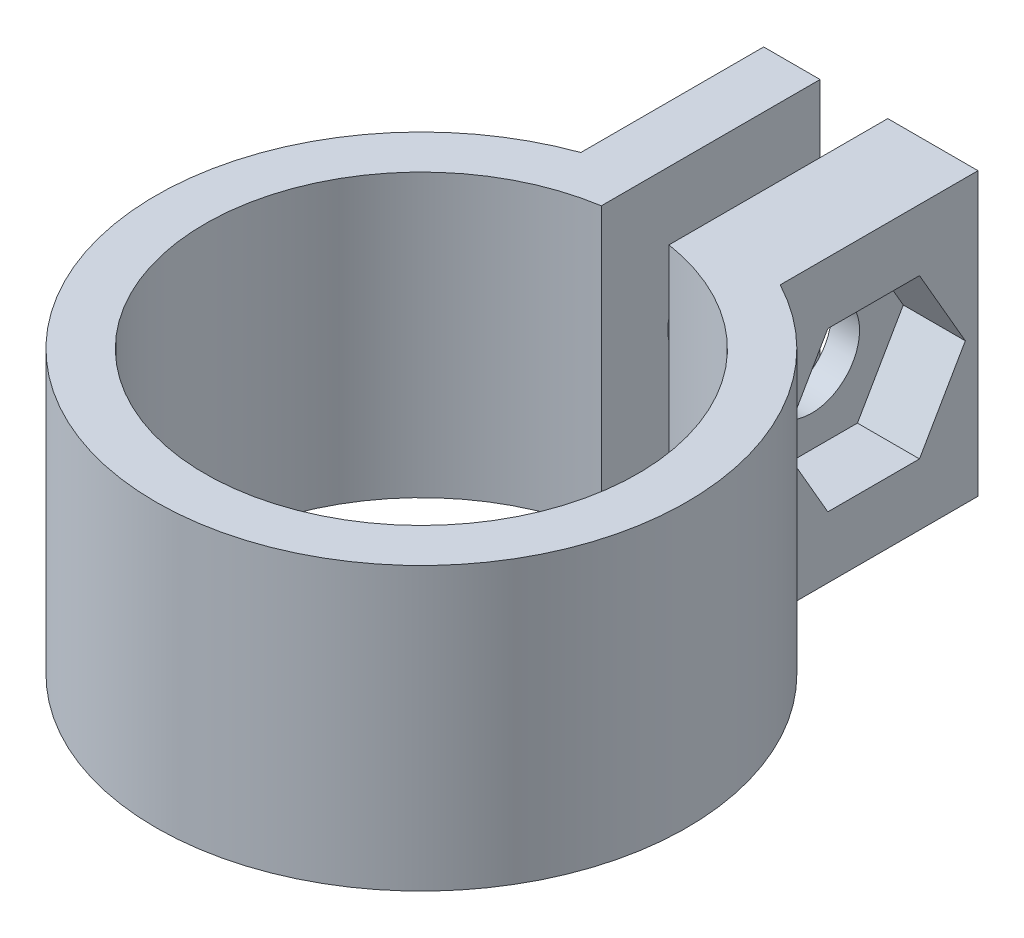
SolidWorks part; units mm, degrees
ref_plane "Front Plane" through (0, 0, 0) normal (0, 0, 1) x (1, 0, 0)
ref_plane "Top Plane" through (0, 0, 0) normal (0, 1, 0) x (1, 0, 0)
ref_plane "Right Plane" through (0, 0, 0) normal (1, 0, 0) x (0, 0, -1)
sketch "Sketch1" plane through (0, 0, 0) normal (0, 1, 0) x (1, 0, 0)
  circle A0 centre (0, 0) radius 7.525 construction
  circle A1 centre (0, 0) radius 7.675
  dimension "D1" = 15.05
  dimension "D2" = 0.15
extrude "Extrude-Thin1" add sketch "Sketch1" along normal blind 10 thin thin type one direction wall 1.74
sketch "Sketch2" plane through (0, 10, 0) normal (0, 1, 0) x (1, 0, 0)
  line L0 (0, 7.0425) -> (0, 0) construction
  line L1 (-1.2, 12.6735) -> (1.2, 12.6735)
  line L2 (-1.2, 12.6735) -> (-1.2, 1.4114)
  line L3 (-1.2, 1.4114) -> (1.2, 1.4114)
  line L4 (1.2, 12.6735) -> (1.2, 1.4114)
  line L5 (-1.2, 12.6735) -> (1.2, 1.4114) construction
  line L6 (-1.2, 1.4114) -> (1.2, 12.6735) construction
  point P0 (0, 7.0425)
  dimension "D1" = 2.4
extrude "Cut-Extrude1" cut sketch "Sketch2" against normal blind 10
ref_plane "Plane1" through (-1.2, 0, 0) normal (1, 0, 0) x (0, 0, -1)
sketch "Sketch4" plane through (-1.2, 0, 0) normal (1, 0, 0) x (0, 0, -1)
  line L0 (9.3382, 10) -> (8.4594, 10)
  line L1 (15.3382, 0) -> (9.3382, 0)
  line L2 (15.3382, 0) -> (15.3382, 10)
  line L3 (15.3382, 10) -> (9.3382, 10)
  line L5 (15.3382, 0) -> (9.3382, 10) construction
  line L6 (15.3382, 10) -> (9.3382, 0) construction
  line L7 (7.5806, 10) -> (9.3382, 10) construction
  line L8 (8.4594, 10) -> (8.4594, 0)
  line L9 (-9.415, 0) -> (9.3382, 0) construction
  line L10 (8.4594, 0) -> (9.3382, 0)
  point P0 (12.3382, 5)
  point P6 (9.3382, 0)
  dimension "D1" = 6
extrude "Boss-Extrude1" add sketch "Sketch4" against normal blind 2
mirror "Mirror1" about plane through (0, 0, 0) normal (1, 0, 0) of "Boss-Extrude1"
sketch "Sketch5" plane through (3.2, 0, 0) normal (1, 0, 0) x (0, 0, -1)
  line L0 (15.3382, 5) -> (11.6382, 5) construction
  line L1 (15.3382, 0) -> (15.3382, 10) construction
  circle A0 centre (11.6382, 5) radius 1.7
  point P3 (15.3382, 5)
  dimension "D1" = 3.4
  dimension "D2" = 2
extrude "Cut-Extrude2" cut sketch "Sketch5" against normal blind 10
other "Move Face1" face at (3.2, 5, -13.3382) offset 1.2 parameters "D1"=1.2
sketch "Sketch7" plane through (4.4, 0, 0) normal (1, 0, 0) x (0, 0, -1)
  line L1 (14.8882, 5) -> (13.2632, 7.8146)
  line L2 (13.2632, 7.8146) -> (10.0132, 7.8146)
  line L3 (10.0132, 7.8146) -> (8.3882, 5)
  line L4 (8.3882, 5) -> (10.0132, 2.1854)
  line L5 (10.0132, 2.1854) -> (13.2632, 2.1854)
  line L6 (13.2632, 2.1854) -> (14.8882, 5)
  circle A0 centre (11.6382, 5) radius 2.8146 construction
  dimension "D1" = 3.25
extrude "Cut-Extrude3" cut sketch "Sketch7" against normal blind 2.2
sketch "Sketch8" plane through (-3.2, 0, 0) normal (-1, 0, 0) x (0, 0, 1)
  circle A0 centre (-11.6382, 5) radius 1.7 construction
  circle A1 centre (-11.6382, 5) radius 1.7 construction
  circle A2 centre (-11.6382, 5) radius 3.25
  dimension "D1" = 6.5
extrude "Cut-Extrude4" cut sketch "Sketch8" along normal blind 3
